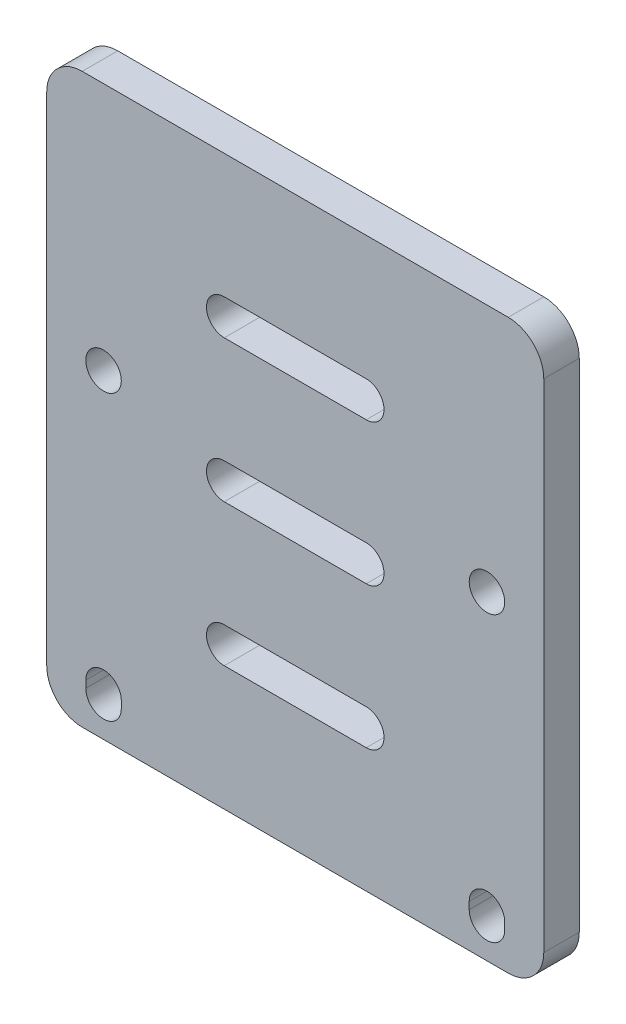
SolidWorks part; units mm, degrees
ref_plane "Front" through (0, 0, 0) normal (0, 0, 1) x (1, 0, 0)
ref_plane "Top" through (0, 0, 0) normal (0, 1, 0) x (1, 0, 0)
ref_plane "Right" through (0, 0, 0) normal (1, 0, 0) x (0, 0, -1)
sketch "Sketch4" plane through (0, 0, 0) normal (0, 0, 1) x (1, 0, 0)
  line L0 (-27, -34) -> (-27, -35) construction
  line L1 (-35, 40) -> (35, 40)
  line L2 (-35, 40) -> (-35, -40)
  line L3 (-35, -40) -> (35, -40)
  line L4 (35, 40) -> (35, -40)
  line L5 (-35, 40) -> (35, -40) construction
  line L6 (-35, -40) -> (35, 40) construction
  line L7 (-24.5, -34) -> (-24.5, -35)
  line L8 (-29.5, -34) -> (-29.5, -35)
  line L9 (0, -47.1607) -> (0, 39.6245) construction
  line L10 (27, -34) -> (27, -35) construction
  line L11 (24.5, -34) -> (24.5, -35)
  line L12 (29.5, -34) -> (29.5, -35)
  line L13 (-21.7344, 0) -> (13.0886, 0) construction
  line L14 (-15, 35) -> (15, 35) construction
  line L15 (-15, 35) -> (-15, -35) construction
  line L16 (-15, -35) -> (15, -35) construction
  line L17 (15, 35) -> (15, -35) construction
  line L18 (-15, 35) -> (15, -35) construction
  line L19 (-15, -35) -> (15, 35) construction
  circle A0 centre (-27, 5) radius 2.5
  arc A1 (-24.5, -34) -> (-29.5, -34) centre (-27, -34) ccw
  arc A2 (-29.5, -35) -> (-24.5, -35) centre (-27, -35) ccw
  arc A3 (24.5, -34) -> (29.5, -34) centre (27, -34) cw
  arc A4 (29.5, -35) -> (24.5, -35) centre (27, -35) cw
  circle A5 centre (27, 5) radius 2.5
  circle A6 centre (-15, 35) radius 1.5 construction
  circle A7 centre (15, 35) radius 1.5 construction
  circle A8 centre (15, -35) radius 1.5 construction
  circle A9 centre (-15, -35) radius 1.5 construction
  point P0 (0, 0)
  point P10 (-27, -34.5)
  point P19 (27, -34.5)
  point P28 (0, 0)
  dimension "D3" = 27
  dimension "D6" = 2.5
  dimension "D8" = 3
  dimension "D1" = 70
  dimension "D2" = 80
  dimension "D4" = 39
  dimension "D5" = 1
  dimension "D7" = 5
  dimension "D9" = 30
  dimension "D10" = 70
extrude "Boss-Extrude2" add sketch "Sketch4" along normal blind 5
fillet "Fillet1" radius 5 4 edges at (-35, -40, 2.5) (35, -40, 2.5) (35, 40, 2.5) (-35, 40, 2.5)
sketch "Sketch6" plane through (0, 0, 5) normal (0, 0, 1) x (1, 0, 0)
  line L3 (0, 21) -> (0, -2.5) construction
  line L4 (-2.5, 0) -> (2.5, 0) construction
  line L8 (-10, 20) -> (10, 20) construction
  line L9 (-10, 22.5) -> (10, 22.5)
  line L10 (-10, 17.5) -> (10, 17.5)
  line L11 (-10, -20) -> (10, -20) construction
  line L24 (-10, 0) -> (10, 0) construction
  line L25 (-10, 2.5) -> (10, 2.5)
  line L26 (-10, -2.5) -> (10, -2.5)
  line L27 (-10, -22.5) -> (10, -22.5)
  line L28 (-10, -17.5) -> (10, -17.5)
  arc A4 (-10, 22.5) -> (-10, 17.5) centre (-10, 20) ccw
  arc A5 (10, 17.5) -> (10, 22.5) centre (10, 20) ccw
  arc A17 (-10, 2.5) -> (-10, -2.5) centre (-10, 0) ccw
  arc A18 (10, -2.5) -> (10, 2.5) centre (10, 0) ccw
  arc A19 (-10, -22.5) -> (-10, -17.5) centre (-10, -20) cw
  arc A20 (10, -17.5) -> (10, -22.5) centre (10, -20) cw
  point P22 (0, 20)
  point P30 (0, -20)
  point P52 (0, 0)
  dimension "D4" = 2.5
  dimension "D5" = 20
  dimension "D7" = 2.5
  dimension "D3" = 20
  dimension "D6" = 20
extrude "Cut-Extrude1" cut sketch "Sketch6" against normal through all
